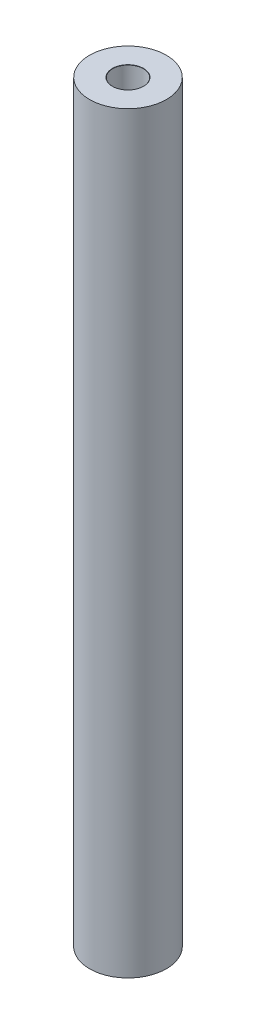
SolidWorks part; units mm, degrees
material "6061-T4 (SS)"
ref_plane "Front Plane" through (0, 0, 0) normal (0, 0, 1) x (1, 0, 0)
ref_plane "Top Plane" through (0, 0, 0) normal (0, 1, 0) x (1, 0, 0)
ref_plane "Right Plane" through (0, 0, 0) normal (1, 0, 0) x (0, 0, -1)
sketch "Sketch1" plane through (0, 0, 0) normal (0, 1, 0) x (1, 0, 0)
  circle A0 centre (0, 0) radius 5
  dimension "D1" = 10
extrude "Boss-Extrude1" add sketch "Sketch1" along normal blind 98
hole_wizard "Ø4.0mm Dowel Hole1" positions "3DSketch1" profile "Sketch4" hole size "Ø4.0" standard "ANSI Metric"
sketch3d "3DSketch1"
  line L0 (0, 98, 0) -> (0, 0, 0) construction
  point P0 (0, 98, 0)
  point P5 (0, 0, 0)
sketch "Sketch4" plane through (0, 98, 0) normal (1, 0, 0) x (0, 0, 1)
  line L0 (0, 0) -> (0, 11.2017)
  line L1 (0, 11.2017) -> (2, 10)
  line L2 (2, 10) -> (2, 0.025)
  line L3 (2, 0.025) -> (2.025, 0)
  line L5 (2.025, 0) -> (0, 0)
  line L6 (-2, 0.025) -> (-2.025, 0) construction
  line L10 (0, 11.2017) -> (-2, 10) construction
  line L11 (0, -6.35) -> (0, 107.95) construction
  dimension "Hole Dia." = 4
  dimension "Hole Depth" = 10
  dimension "Near C'Sink Dia." = 4.05
  dimension "Near C'Sink Angle" = 90
  dimension "Drill Angle" = 118
cosmetic thread "Cosmetic Thread1" parameters "D2"=5
ref_plane "Plane3" through (0, 49, 0) normal (0, 1, 0) x (1, 0, 0)
mirror "Mirror1" about plane through (0, 49, 0) normal (0, 1, 0) of "Ø4.0mm Dowel Hole1"
cosmetic thread "Cosmetic Thread2" parameters "D2"=5
equation "\"D1@Boss-Extrude1\"=98"
